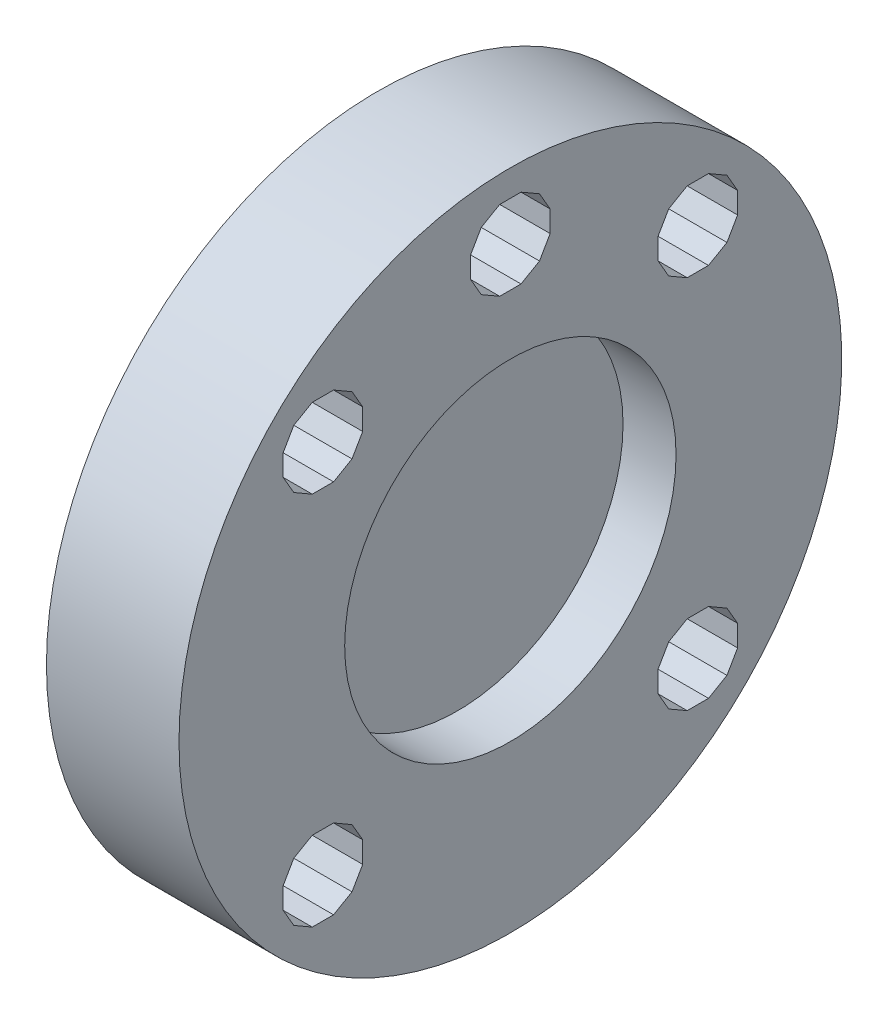
SolidWorks part; units mm, degrees
ref_plane "Front Plane" through (0, 0, 0) normal (0, 0, 1) x (1, 0, 0)
ref_plane "Top Plane" through (0, 0, 0) normal (0, 1, 0) x (1, 0, 0)
ref_plane "Right Plane" through (0, 0, 0) normal (1, 0, 0) x (0, 0, -1)
ref_plane "Plane1" through (0, 0, 0) normal (0, 0, -1) x (-1, 0, 0)
sketch "Sketch1" plane through (0, 0, 0) normal (0, 0, -1) x (-1, 0, 0)
  line L0 (-5, 25) -> (-5, 0)
  line L1 (-5, 0) -> (5, 0)
  line L2 (5, 0) -> (5, 25)
  line L3 (5, 25) -> (-5, 25)
  line L4 (-5, 0) -> (5, 0) construction
revolve "Revolve1" add sketch "Sketch1" angle 360 about L4 reverse direction yes
sketch "Sketch2" plane through (-5, 0, 0) normal (-1, 0, 0) x (0, 0, 1)
  line L0 (0.8038, 17) -> (2.1962, 17.8038)
  line L1 (2.1962, 17.8038) -> (3, 19.1962)
  line L2 (3, 19.1962) -> (3, 20.8038)
  line L3 (3, 20.8038) -> (2.1962, 22.1962)
  line L4 (2.1962, 22.1962) -> (0.8038, 23)
  line L5 (0.8038, 23) -> (-0.8038, 23)
  line L6 (-0.8038, 23) -> (-2.1962, 22.1962)
  line L7 (-2.1962, 22.1962) -> (-3, 20.8038)
  line L8 (-3, 20.8038) -> (-3, 19.1962)
  line L9 (-3, 19.1962) -> (-2.1962, 17.8038)
  line L10 (-2.1962, 17.8038) -> (-0.8038, 17)
  line L11 (-0.8038, 17) -> (0.8038, 17)
extrude "Cut-Extrude1" cut sketch "Sketch2" against normal through all
sketch "Sketch3" plane through (-5, 0, 0) normal (-1, 0, 0) x (0, 0, 1)
  line L0 (-13.3383, -17.1421) -> (-11.946, -16.3383)
  line L1 (-11.946, -16.3383) -> (-11.1421, -14.946)
  line L2 (-11.1421, -14.946) -> (-11.1421, -13.3383)
  line L3 (-11.1421, -13.3383) -> (-11.946, -11.946)
  line L4 (-11.946, -11.946) -> (-13.3383, -11.1421)
  line L5 (-13.3383, -11.1421) -> (-14.946, -11.1421)
  line L6 (-14.946, -11.1421) -> (-16.3383, -11.946)
  line L7 (-16.3383, -11.946) -> (-17.1421, -13.3383)
  line L8 (-17.1421, -13.3383) -> (-17.1421, -14.946)
  line L9 (-17.1421, -14.946) -> (-16.3383, -16.3383)
  line L10 (-16.3383, -16.3383) -> (-14.946, -17.1421)
  line L11 (-14.946, -17.1421) -> (-13.3383, -17.1421)
extrude "Cut-Extrude2" cut sketch "Sketch3" against normal through all
sketch "Sketch4" plane through (-5, 0, 0) normal (-1, 0, 0) x (0, 0, 1)
  line L0 (14.946, -17.1421) -> (16.3383, -16.3383)
  line L1 (16.3383, -16.3383) -> (17.1421, -14.946)
  line L2 (17.1421, -14.946) -> (17.1421, -13.3383)
  line L3 (17.1421, -13.3383) -> (16.3383, -11.946)
  line L4 (16.3383, -11.946) -> (14.946, -11.1421)
  line L5 (14.946, -11.1421) -> (13.3383, -11.1421)
  line L6 (13.3383, -11.1421) -> (11.946, -11.946)
  line L7 (11.946, -11.946) -> (11.1421, -13.3383)
  line L8 (11.1421, -13.3383) -> (11.1421, -14.946)
  line L9 (11.1421, -14.946) -> (11.946, -16.3383)
  line L10 (11.946, -16.3383) -> (13.3383, -17.1421)
  line L11 (13.3383, -17.1421) -> (14.946, -17.1421)
extrude "Cut-Extrude3" cut sketch "Sketch4" against normal through all
sketch "Sketch5" plane through (-5, 0, 0) normal (-1, 0, 0) x (0, 0, 1)
  line L0 (16.3383, 11.946) -> (17.1421, 13.3383)
  line L1 (17.1421, 13.3383) -> (17.1421, 14.946)
  line L2 (17.1421, 14.946) -> (16.3383, 16.3383)
  line L3 (16.3383, 16.3383) -> (14.946, 17.1421)
  line L4 (14.946, 17.1421) -> (13.3383, 17.1421)
  line L5 (13.3383, 17.1421) -> (11.946, 16.3383)
  line L6 (11.946, 16.3383) -> (11.1421, 14.946)
  line L7 (11.1421, 14.946) -> (11.1421, 13.3383)
  line L8 (11.1421, 13.3383) -> (11.946, 11.946)
  line L9 (11.946, 11.946) -> (13.3383, 11.1421)
  line L10 (13.3383, 11.1421) -> (14.946, 11.1421)
  line L11 (14.946, 11.1421) -> (16.3383, 11.946)
extrude "Cut-Extrude4" cut sketch "Sketch5" against normal through all
sketch "Sketch6" plane through (5, 0, 0) normal (1, 0, 0) x (0, 0, -1)
  line L0 (16.3383, 11.946) -> (17.1421, 13.3383)
  line L1 (17.1421, 13.3383) -> (17.1421, 14.946)
  line L2 (17.1421, 14.946) -> (16.3383, 16.3383)
  line L3 (16.3383, 16.3383) -> (14.946, 17.1421)
  line L4 (14.946, 17.1421) -> (13.3383, 17.1421)
  line L5 (13.3383, 17.1421) -> (11.946, 16.3383)
  line L6 (11.946, 16.3383) -> (11.1421, 14.946)
  line L7 (11.1421, 14.946) -> (11.1421, 13.3383)
  line L8 (11.1421, 13.3383) -> (11.946, 11.946)
  line L9 (11.946, 11.946) -> (13.3383, 11.1421)
  line L10 (13.3383, 11.1421) -> (14.946, 11.1421)
  line L11 (14.946, 11.1421) -> (16.3383, 11.946)
extrude "Cut-Extrude5" cut sketch "Sketch6" against normal through all
sketch "Sketch7" plane through (-5, 0, 0) normal (-1, 0, 0) x (0, 0, 1)
  line L0 (8.2331, -8.2331) -> (5.286, -10.3743)
  line L1 (5.286, -10.3743) -> (1.8214, -11.5)
  line L2 (1.8214, -11.5) -> (-1.8214, -11.5)
  line L3 (-1.8214, -11.5) -> (-5.286, -10.3743)
  line L4 (-5.286, -10.3743) -> (-8.2331, -8.2331)
  line L5 (-8.2331, -8.2331) -> (-10.3743, -5.286)
  line L6 (-10.3743, -5.286) -> (-11.5, -1.8214)
  line L7 (-11.5, -1.8214) -> (-11.5, 1.8214)
  line L8 (-11.5, 1.8214) -> (-10.3743, 5.286)
  line L9 (-10.3743, 5.286) -> (-8.2331, 8.2331)
  line L10 (-8.2331, 8.2331) -> (-5.286, 10.3743)
  line L11 (-5.286, 10.3743) -> (-1.8214, 11.5)
  line L12 (-1.8214, 11.5) -> (1.8214, 11.5)
  line L13 (1.8214, 11.5) -> (5.286, 10.3743)
  line L14 (5.286, 10.3743) -> (8.2331, 8.2331)
  line L15 (8.2331, 8.2331) -> (10.3743, 5.286)
  line L16 (10.3743, 5.286) -> (11.5, 1.8214)
  line L17 (11.5, 1.8214) -> (11.5, -1.8214)
  line L18 (11.5, -1.8214) -> (10.3743, -5.286)
  line L19 (10.3743, -5.286) -> (8.2331, -8.2331)
extrude "Boss-Extrude1" add sketch "Sketch7" along normal blind 1.5
hole_wizard "Ø25.0 (25) Diameter Hole1" positions "Sketch9" profile "Sketch8" hole size "Ø25.0" standard "ANSI Metric"
sketch "Sketch9" plane through (5, 0, 0) normal (1, 0, 0) x (0, 0, -1)
  point P0 (0, 0)
sketch "Sketch8" plane through (5, 0, 0) normal (0, 1, 0) x (0, 0, -1)
  line L0 (0, 0) -> (0, 4)
  line L1 (0, 4) -> (12.5, 4)
  line L2 (12.5, 4) -> (12.5, 0)
  line L5 (12.5, 0) -> (0, 0)
  line L10 (0, 4) -> (-12.5, 4) construction
  line L11 (0, -6.35) -> (0, 107.95) construction
  dimension "Hole Dia." = 25
  dimension "Hole Depth" = 4
  dimension "Drill Angle" = 180
ref_axis "Axis1" through (5, 0, 0) along (-1, 0, 0)
sketch "Sketch11" plane through (5, 0, 0) normal (1, 0, 0) x (0, 0, -1)
  line L0 (2.1962, 17.8038) -> (0.8038, 17) construction
  line L1 (-3, 19.1962) -> (-3, 20.8038) construction
  line L2 (2.1962, 22.1962) -> (3, 20.8038) construction
  circle A0 centre (0, 20) radius 3
ref_axis "Axis3" through (5, 20, 0) along (-1, 0, 0)
